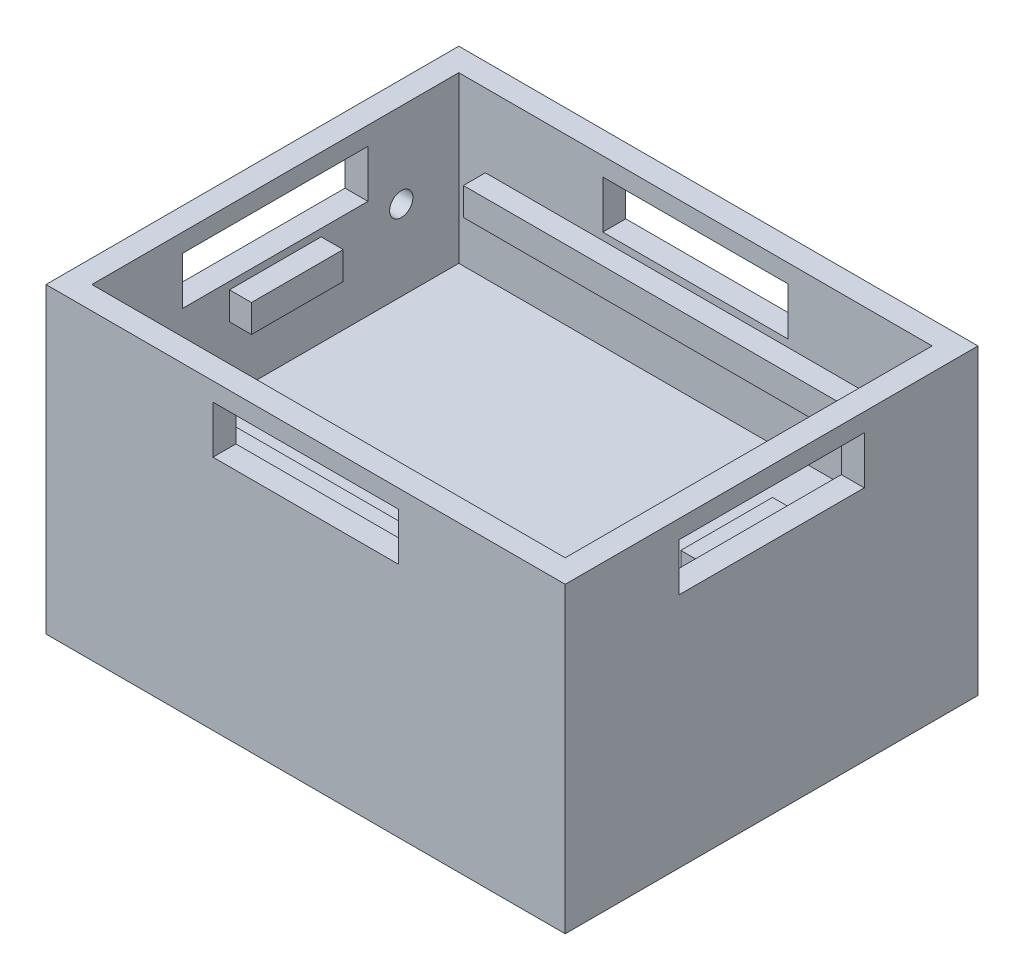
SolidWorks part; units mm, degrees
ref_plane "Front Plane" through (0, 0, 0) normal (0, 0, 1) x (1, 0, 0)
ref_plane "Top Plane" through (0, 0, 0) normal (0, 1, 0) x (1, 0, 0)
ref_plane "Right Plane" through (0, 0, 0) normal (1, 0, 0) x (0, 0, -1)
sketch "Sketch1" plane through (0, 0, 0) normal (0, 1, 0) x (1, 0, 0)
  line L0 (-2.5, 2.5) -> (-2.5, 202.5)
  line L5 (-15, -10) -> (268, -10)
  line L6 (-15, -10) -> (-15, 215)
  line L7 (-15, 215) -> (268, 215)
  line L8 (268, -10) -> (268, 215)
  line L9 (-2.5, 202.5) -> (255.5, 202.5)
  line L10 (255.5, 2.5) -> (255.5, 202.5)
  line L11 (-2.5, 2.5) -> (255.5, 2.5)
  dimension "D1" = 283
  dimension "D2" = 225
  dimension "D3" = 12.5
extrude "Walls" add sketch "Sketch1" along normal blind 90
sketch "Sketch3" plane through (0, 0, 0) normal (0, -1, 0) x (1, 0, 0)
  line L0 (268, -215) -> (-15, -215) construction
  line L1 (268, 10) -> (268, -215) construction
  line L2 (-15, 10) -> (268, 10) construction
  line L3 (-15, -215) -> (-15, 10) construction
  line L4 (268, -215) -> (-15, -215)
  line L5 (268, 10) -> (268, -215)
  line L6 (-15, 10) -> (268, 10)
  line L7 (-15, -215) -> (-15, 10)
extrude "Base" add sketch "Sketch3" along normal blind 12.5
ref_plane "Long_Support_Midplane" through (126.5, 0, 0) normal (1, 0, 0) x (0, 0, -1)
sketch "Sketch4" plane through (126.5, 0, 0) normal (1, 0, 0) x (0, 0, -1)
  line L0 (2.5, 0) -> (2.5, 90)
  line L1 (2.5, 50) -> (14.5, 50)
  line L2 (2.5, 50) -> (2.5, 34.9)
  line L3 (2.5, 34.9) -> (14.5, 34.9)
  line L4 (14.5, 50) -> (14.5, 34.9)
  line L5 (2.5, 0) -> (2.5, 90) construction
  line L6 (202.5, 50) -> (190.5, 50)
  line L7 (202.5, 50) -> (202.5, 34.9)
  line L8 (202.5, 34.9) -> (190.5, 34.9)
  line L9 (190.5, 50) -> (190.5, 34.9)
  line L14 (2.5, 0) -> (202.5, 0)
  line L15 (202.5, 0) -> (202.5, 90)
  line L16 (202.5, 90) -> (2.5, 90)
  line L17 (2.5, 90) -> (2.5, 0)
  line L18 (2.5, 0) -> (202.5, 0) construction
  line L19 (202.5, 0) -> (202.5, 90) construction
  line L20 (202.5, 90) -> (2.5, 90) construction
  line L21 (2.5, 90) -> (2.5, 0) construction
  dimension "D1" = 15.1
  dimension "D2" = 12
  dimension "D4" = 50
extrude "Long_Support" add sketch "Sketch4" along normal mid plane 229
ref_plane "Short_Support_Midplane" through (0, 0, -102.5) normal (0, 0, -1) x (-1, 0, 0)
sketch "Sketch5" plane through (0, 0, -102.5) normal (0, 0, -1) x (-1, 0, 0)
  line L1 (-255.5, 50) -> (-243.5, 50)
  line L2 (-255.5, 50) -> (-255.5, 34.9)
  line L3 (-255.5, 34.9) -> (-243.5, 34.9)
  line L4 (-243.5, 50) -> (-243.5, 34.9)
  line L5 (2.5, 50) -> (-9.5, 50)
  line L6 (2.5, 50) -> (2.5, 34.9)
  line L7 (2.5, 34.9) -> (-9.5, 34.9)
  line L8 (-9.5, 50) -> (-9.5, 34.9)
  line L12 (-255.5, 0) -> (2.5, 0)
  line L13 (2.5, 0) -> (2.5, 90)
  line L14 (2.5, 90) -> (-255.5, 90)
  line L15 (2.5, 0) -> (2.5, 90) construction
  line L16 (-255.5, 0) -> (2.5, 0) construction
  line L20 (-255.5, 90) -> (-255.5, 0)
  line L21 (-255.5, 90) -> (-255.5, 0) construction
  line L22 (2.5, 90) -> (-255.5, 90) construction
  dimension "D4" = 50
  dimension "D2" = 15.1
extrude "Short_Support" add sketch "Sketch5" along normal mid plane 50
sketch "Sketch6" plane through (-2.5, 0, 0) normal (1, 0, 0) x (0, 0, -1)
  line L4 (2.5, 0) -> (202.5, 0)
  line L5 (202.5, 0) -> (202.5, 90)
  line L6 (202.5, 90) -> (2.5, 90)
  line L7 (2.5, 90) -> (2.5, 0)
  line L8 (2.5, 0) -> (202.5, 0) construction
  line L9 (202.5, 0) -> (202.5, 90) construction
  line L10 (202.5, 90) -> (2.5, 90) construction
  line L11 (2.5, 90) -> (2.5, 0) construction
  circle A0 centre (171.15, 43.65) radius 6.35
  dimension "D2" = 12.7
  dimension "D3" = 31.35
  dimension "D4" = 43.65
extrude "Reservoir_Outflow_Tube_Hole" cut sketch "Sketch6" against normal up to next
sketch "Sketch7" plane through (-2.5, 0, 0) normal (1, 0, 0) x (0, 0, -1)
  line L0 (127.5, 50) -> (77.5, 50) construction
  line L1 (52, 54) -> (153, 54)
  line L2 (52, 54) -> (52, 80)
  line L3 (52, 80) -> (153, 80)
  line L4 (153, 54) -> (153, 80)
  line L5 (202.5, 90) -> (2.5, 90) construction
  line L7 (102.5, 80) -> (102.5, 54) construction
  line L8 (102.5, -27.5) -> (102.5, 27.5) construction
  dimension "D1" = 4
  dimension "D2" = 10
  dimension "D3" = 26
  dimension "D4" = 101
extrude "Connector_Port_ShortSide" cut sketch "Sketch7" against normal up to surface (12.5 mm away) up to face at (-15, 43.65, -177.5)
pattern_linear "LPattern1" count 2 spacing 270.5 along (1, 0, 0) of "Connector_Port_ShortSide"
sketch "Sketch8" plane through (0, 0, -2.5) normal (0, 0, 1) x (1, 0, 0)
  line L1 (76, 54) -> (177, 54)
  line L2 (76, 54) -> (76, 80)
  line L3 (76, 80) -> (177, 80)
  line L4 (177, 54) -> (177, 80)
  line L6 (241, 50) -> (12, 50) construction
  line L7 (126.5, 80) -> (126.5, 54) construction
  line L9 (-2.5, 90) -> (255.5, 90) construction
  line L10 (126.5, -28.05) -> (126.5, 28.05) construction
  dimension "D3" = 26
  dimension "D4" = 101
  dimension "D1" = 4
  dimension "D2" = 10
extrude "Connector_Port_LongSide" cut sketch "Sketch8" along normal up to surface (12.5 mm away) contours L4 L3 L2 L1 up to face at (126.5, 38.75, 10)
pattern_linear "LPattern2" count 2 spacing 212.5 along (0, 0, -1) of "Connector_Port_LongSide"
sketch "Sketch9" plane through (0, -12.5, 0) normal (0, -1, 0) x (1, 0, 0)
  line L10 (268, -215) -> (268, 10) construction
  line L11 (-15, -215) -> (268, -215) construction
  line L12 (268, 10) -> (-15, 10) construction
  line L13 (-15, 10) -> (-15, -215) construction
  line L14 (-2.5, -202.5) -> (255.5, -202.5)
  line L15 (255.5, -202.5) -> (255.5, -2.5)
  line L16 (255.5, -2.5) -> (-2.5, -2.5)
  line L17 (-2.5, -2.5) -> (-2.5, -202.5)
  line L18 (-2.5, -202.5) -> (255.5, -202.5)
  line L19 (255.5, -202.5) -> (255.5, -2.5)
  line L20 (255.5, -2.5) -> (-2.5, -2.5)
  line L21 (-2.5, -2.5) -> (-2.5, -202.5)
  line L22 (268, -215) -> (268, 10)
  line L23 (-15, -215) -> (268, -215)
  line L24 (268, 10) -> (-15, 10)
  line L25 (-15, 10) -> (-15, -215)
  dimension "D1" = 12.5
extrude "Lower_Water_Jacket_Walls" add sketch "Sketch9" along normal blind 50
sketch "Sketch11" plane through (0, -62.5, 0) normal (0, -1, 0) x (1, 0, 0)
  line L0 (-15, -215) -> (268, -215) construction
  line L1 (268, -215) -> (268, 10) construction
  line L2 (268, 10) -> (-15, 10) construction
  line L3 (-15, 10) -> (-15, -215) construction
  line L4 (-15, -215) -> (268, -215)
  line L5 (268, -215) -> (268, 10)
  line L6 (268, 10) -> (-15, 10)
  line L7 (-15, 10) -> (-15, -215)
extrude "Lower_Water_Jacket_Bottom" add sketch "Sketch11" along normal blind 12.5
equation "\"Length\"= 283"
equation "\"Width\"= 225"
equation "\"WallThickness\"= 12.5"
equation "\"UpperWaterJacketThickness\"= 28"
equation "\"SpacerHeight\"= 80.2"
equation "\"PlateLength\"=252"
equation "\"PlateWidth\"=190"
equation "\"PlateHoleDiameter\"=5.9"
equation "\"PlateHoleBottom\"= 2"
equation "\"PlateHoleSide\"= 1.55"
equation "\"PlateHoleSpacing\"= 3.1"
equation "\"PlateThickness\"=1.55"
equation "\"D1@Sketch1\"=\"Length\""
equation "\"D2@Sketch1\"=\"Width\""
equation "\"D3@Sketch1\"=\"WallThickness\""
equation "\"ReservoirBottom\"=12.5"
equation "\"D1@Base\"=\"ReservoirBottom\""
equation "\"ReservoirSupportWidth\"=12"
equation "\"D2@Sketch4\"=\"ReservoirSupportWidth\""
equation "\"ReservoirSupportHeight\"=15.1"
equation "\"D1@Sketch4\"=\"ReservoirSupportHeight\""
equation "\"D1@Sketch5\"=\"ReservoirSupportWidth\""
equation "\"D2@Sketch5\"=\"ReservoirSupportHeight\""
equation "\"ReservoirSupportPlacementHeight\"=50"
equation "\"D4@Sketch5\"=\"ReservoirSupportPlacementHeight\""
equation "\"D4@Sketch4\"=\"ReservoirSupportPlacementHeight\""
equation "\"ReservoirHoleDiameter\"=12.7"
equation "\"D2@Sketch6\"=\"ReservoirHoleDiameter\""
equation "\"ReservoirHoleRight\"= 25"
equation "\"D3@Sketch6\"=\"ReservoirHoleRight\"+\"ReservoirHoleDiameter\"/2"
equation "\"ReservoirHoleTop\"= \"ReservoirSupportPlacementHeight\""
equation "\"D4@Sketch6\"=\"ReservoirHoleTop\"-\"ReservoirHoleDiameter\"/2"
equation "\"ReservoirHeight\"=90"
equation "\"D1@Walls\"=\"ReservoirHeight\""
equation "\"ReservoirPortBottom\"=4"
equation "\"D1@Sketch7\"=\"ReservoirPortBottom\""
equation "\"ReservoirPortTop\"= 10"
equation "\"D2@Sketch7\"=\"ReservoirPortTop\""
equation "\"ReservoirPortWidth\"=101"
equation "\"D4@Sketch7\"=\"ReservoirPortWidth\""
equation "\"D4@Sketch8\"=\"ReservoirPortWidth\""
equation "\"D1@Sketch8\"=\"ReservoirPortBottom\""
equation "\"D2@Sketch8\"=\"ReservoirPortTop\""
equation "\"D1@Sketch9\"=\"WallThickness\""
equation "\"LowerWaterJacketHeight\"= 50"
equation "\"D1@Lower_Water_Jacket_Walls\" = \"LowerWaterJacketHeight\""
equation "\"LowerWaterJacketBottomThickness\"= \"WallThickness\""
equation "\"D1@Lower_Water_Jacket_Bottom\" = \"LowerWaterJacketBottomThickness\""
